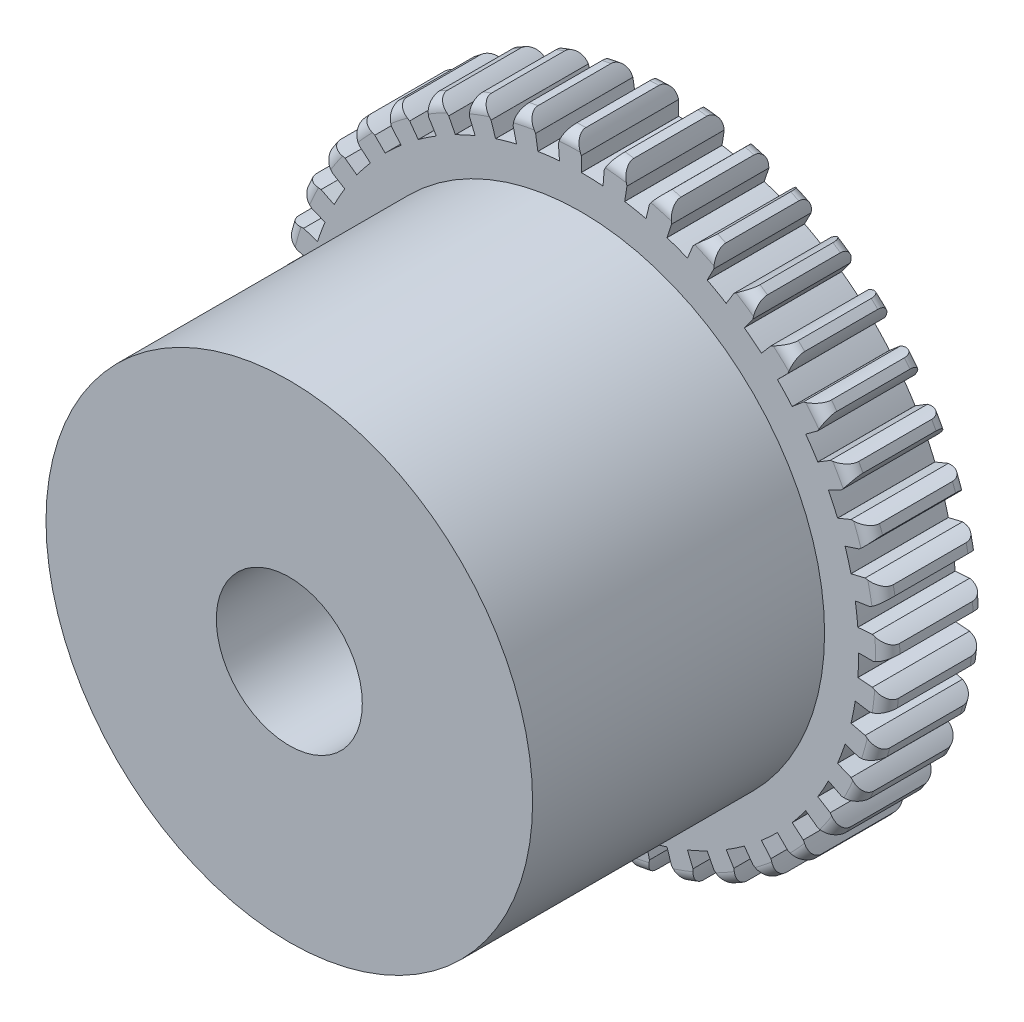
SolidWorks part; units mm, degrees
ref_plane "Front Plane" through (0, 0, 0) normal (0, 0, 1) x (1, 0, 0)
ref_plane "Top Plane" through (0, 0, 0) normal (0, 1, 0) x (1, 0, 0)
ref_plane "Right Plane" through (0, 0, 0) normal (1, 0, 0) x (0, 0, -1)
ref_axis "Rotation_Axis" through (0, 0, -2.2) along (0, 0, 1)
sketch "Outer_Profile" plane through (0, 0, 0) normal (0, 0, 1) x (1, 0, 0)
  circle A0 centre (0, 0) radius 6.3
  dimension "D1" = 12.6
extrude "Main_Wheel" add sketch "Outer_Profile" along normal mid plane 2
sketch "Tooth_Profile" plane through (0, 0, 0) normal (0, 0, 1) x (1, 0, 0)
  line L0 (0, 0) -> (0, 6.3) construction
  line L1 (0, 0) -> (-0.4943, 6.2806) construction
  line L2 (-13.9134, 0.9359) -> (0, 6) construction
  line L3 (0, 6) -> (-12.8221, 6) construction
  line L4 (0, 0) -> (-0.2525, 6.4276) construction
  line L5 (0, 5.9998) -> (0, 5.701)
  line L6 (0, 0) -> (0.9789, 8.2711) construction
  line L7 (0, 0) -> (0.2473, 6.2951) construction
  line L8 (0.4707, 5.9813) -> (0.4473, 5.6834)
  line L9 (-0.2525, 6.4276) -> (-0.2717, 6.916)
  line L10 (-0.2717, 6.916) -> (0.8135, 6.8734)
  line L11 (0.8135, 6.8734) -> (0.7561, 6.388)
  circle A0 centre (0, 0) radius 5.7 construction
  circle A1 centre (0, 0) radius 6.3 construction
  circle A2 centre (0, 0) radius 6 construction
  circle A3 centre (0, 0) radius 6.3 construction
  circle A4 centre (0, 0) radius 5.6382 construction
  circle A5 centre (0, 6) radius 1.5 construction
  circle A6 centre (-1.4, 5.4616) radius 1.5 construction
  arc A7 (-0.2525, 6.4276) -> (-0.0001, 6.0002) centre (-1.4, 5.4616) cw
  arc A9 (0.7561, 6.388) -> (0.4708, 5.9817) centre (1.8242, 5.3349) ccw
  arc A11 (0.001, 5.7) -> (0.4462, 5.6825) centre (0, 0) cw
  arc A12 (0.4473, 5.6834) -> (0.4462, 5.6825) centre (0.4463, 5.6835) cw
  arc A13 (0.001, 5.7) -> (0, 5.701) centre (0.001, 5.701) cw
  arc A14 (0.4708, 5.9817) -> (0.4707, 5.9813) centre (0.4717, 5.9812) ccw
  arc A15 (0, 5.9998) -> (-0.0001, 6.0002) centre (-0.001, 5.9998) ccw
  circle A18 centre (0.2473, 6.2951) radius 0.6 construction
  point P31 (0.4472, 5.6824)
  point P34 (0, 5.7)
  point P37 (0.4708, 5.9815)
  point P43 (0.7561, 6.388)
  point P46 (-0.2525, 6.4276)
  dimension "D1" = 11.4
  dimension "D2" = 12
  dimension "D6" = 3
  dimension "D9" = 0.001
  dimension "D10" = 0.001
  dimension "D3" = 4.5
  dimension "D4" = 2.25
  dimension "D5" = 20
  dimension "D8" = 4.5
  dimension "D7" = 9
extrude "Tooth_Cut" cut sketch "Tooth_Profile" along normal through all both and the other way through all
pattern_circular "CirPattern1" count 40 over 360 about axis through (0, 0, 0) along (0, 0, 1) of "Tooth_Cut"
sketch "Sketch4" plane through (0, 0, 0) normal (0, 1, 0) x (1, 0, 0)
  line L0 (-6.3, 0) -> (-6.3, 0.75)
  line L2 (-6.05, 1) -> (-3.4269, 1)
  line L5 (-3.4269, 3.2114) -> (-9.247, 3.2114)
  line L6 (-9.247, 3.2114) -> (-9.247, -3.2114)
  line L7 (-9.247, -3.2114) -> (-3.4269, -3.2114)
  line L9 (-3.4269, -1) -> (-6.05, -1)
  line L10 (-6.3, -0.75) -> (-6.3, 0)
  line L12 (-0.9387, 1) -> (-1.1383, 1) construction
  line L13 (-3.4269, 3.2114) -> (-3.4269, 1)
  line L14 (-3.4269, -1) -> (-3.4269, -3.2114)
  arc A0 (-6.05, -1) -> (-6.3, -0.75) centre (-6.05, -0.75) cw
  arc A1 (-6.05, 1) -> (-6.3, 0.75) centre (-6.05, 0.75) ccw
  dimension "D1" = 0.25
revolve "Gear_tooth_fillets" cut sketch "Sketch4" angle 360 about axis through (0, 0, -2.2) along (0, 0, 1)
sketch "Sketch3" plane through (0, 0, 0) normal (0, 0, 1) x (1, 0, 0)
  circle A0 centre (0, 0) radius 6.3
  dimension "D1" = 12.6
extrude "Outer_tooth_limit" [suppressed] cut sketch "Sketch3" against normal through all both and the other way through all thin
sketch "Sketch5" plane through (0, 0, 1) normal (0, 0, 1) x (1, 0, 0)
  circle A0 centre (0, 0) radius 5
  dimension "D1" = 10
extrude "Extended_Mount" add sketch "Sketch5" along normal blind 6
sketch "Sketch6" plane through (0, 0, 7) normal (0, 0, 1) x (1, 0, 0)
  circle A0 centre (0, 0) radius 1.5
  dimension "D1" = 3
extrude "Shaft" cut sketch "Sketch6" against normal through all both and the other way through all
equation "\"D_Outer\"= ( \"N\" + 2 ) / \"Pitch\""
equation "\"N\"= 40'Driving Dimension"
equation "\"Pitch\"= \"N\" / \"D_Pitch\""
equation "\"D_Pitch\"= 12'Driving Dimension"
equation "\"D_Inner\"= ( \"N\" - 2 ) / \"Pitch\""
equation "\"Circular_thickness_angle\"= 0.5 * 360 / \"N\""
equation "\"D1@Outer_Profile\" = \"D_Outer\""
equation "\"D1@Tooth_Profile\"=\"D_Inner\""
equation "\"D2@Tooth_Profile\"=\"D_Pitch\""
equation "\"D3@Tooth_Profile\"=\"Circular_thickness_angle\""
equation "\"Bisecting_angle\"= \"Circular_thickness_angle\" / 2"
equation "\"D4@Tooth_Profile\"=\"Bisecting_angle\""
equation "\"Pressure_Angle\"= 20'Driving Dimension"
equation "\"D5@Tooth_Profile\"=\"Pressure_Angle\""
equation "\"D6@Tooth_Profile\"=\"D_Pitch\"/8*2"
equation "\"D8@Tooth_Profile\"=(360/2)/\"N\""
equation "\"D7@Tooth_Profile\"=360/\"N\""
equation "\"Fillet_Root\"= .001mm"
equation "\"Fillet_Pressure\"= .001mm"
equation "\"D9@Tooth_Profile\"=\"Fillet_Root\""
equation "\"D10@Tooth_Profile\"=\"Fillet_Pressure\""
equation "\"D1@CirPattern1\"=\"N\""
equation "\"D_shaft\"= 3'Driving Dimension"
equation "\"D_extended_mount\"= 10'Driving Dimension"
equation "\"L_extended_mount\"= 6'Driving Dimension"
equation "\"D1@Extended_Mount\"=\"L_extended_mount\""
equation "\"L_gear\"= 2mm'Driving Dimension"
equation "\"D1@Sketch6\"=\"D_shaft\""
equation "\"D1@Main_Wheel\"=\"L_gear\""
